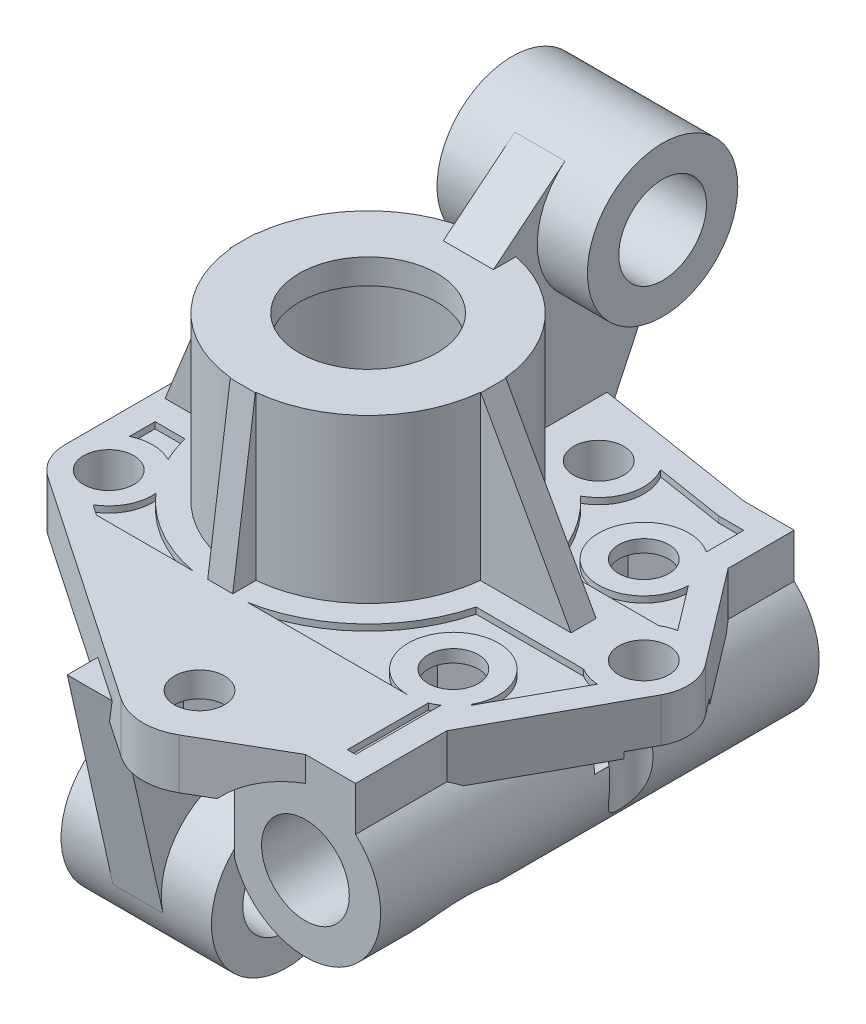
SolidWorks part; units mm, degrees
note: '?' marks a value the reader was unsure of.
ref_plane "Front Plane" through (0, 0, 0) normal (0, 0, 1) x (1, 0, 0)
ref_plane "Top Plane" through (0, 0, 0) normal (0, 1, 0) x (1, 0, 0)
ref_plane "Right Plane" through (0, 0, 0) normal (1, 0, 0) x (0, 0, -1)
ref_plane "StagePlane" through (0, -6, 0) normal (0, 1, 0) x (-1, 0, 0)
sketch "Sketch4" plane through (0, 0, 0) normal (0, 1, 0) x (1, 0, 0)
  circle A0 centre (0, 0) radius 10
  dimension "D3" = 20
extrude "Boss-Extrude5" add sketch "Sketch4" along normal mid plane 30
ref_axis "Axis2" through (0, -15, 0) along (0, 1, 0)?
sketch "Sketch8" plane through (0, 0, 0) normal (1, 0, 0) x (0, 0, -1)
  line L0 (6, 20.2975) -> (6, -9.7025) construction
  line L1 (0, -15) -> (0, 15) construction
  line L2 (55, 0) -> (-55, 0) construction
  line L3 (13.7105, 19.6519) -> (8, 15)
  line L4 (10, 15) -> (-10, 15) construction
  line L5 (10, -15) -> (10, 15) construction
  line L6 (-18.3556, -16.3085) -> (-22, 0)
  line L7 (17.0662, 0) -> (22.9279, 12.443)
  line L8 (17.0662, 0) -> (8, 0)
  line L9 (-6.5, 0) -> (-22, 0)
  line L10 (-10, -15) -> (10, -15) construction
  line L11 (10, -15) -> (17.0662, 0) construction
  line L12 (-6.5, -15) -> (-6.5, 0)
  line L13 (8, 15) -> (8, 0)
  line L14 (-10, 15) -> (-10, -15) construction
  circle A0 centre (17.5, 15) radius 3.5
  circle A1 centre (-12.5, -15) radius 3.5
  arc A2 (-18.3556, -16.3085) -> (-6.5, -15) centre (-12.5, -15) ccw
  arc A3 (22.9279, 12.443) -> (13.7105, 19.6519) centre (17.5, 15) ccw
  dimension "D5" = 7
  dimension "D7" = 12
  dimension "D1" = 6
  dimension "D2" = 30
  dimension "D3" = 30
  dimension "D4" = 11.5
  dimension "D6" = 15
  dimension "D8" = 2
  dimension "D9" = 12
extrude "Boss-Extrude6" add sketch "Sketch8" along normal mid plane 4
sketch "Sketch16" plane through (0, 0, 0) normal (0, 0, 1) x (1, 0, 0)
  line L0 (9, -6) -> (9, 2)
  line L1 (9, 2) -> (19, 2)
  line L2 (19, 2) -> (19, -1.5279)
  line L3 (0, -15) -> (0, 15) construction
  line L6 (15, -6) -> (15, 11.8947) construction
  line L11 (22.825, -6) -> (-22.825, -6) construction
  arc A0 (9, -6) -> (19, -1.5279) centre (15, -6) ccw
  circle A2 centre (15, -6) radius 3.5
  dimension "D2" = 8
  dimension "D4" = 7
  dimension "D5" = 6
  dimension "D1" = 4
  dimension "D3" = 15
extrude "Boss-Extrude10" add sketch "Sketch16" along normal blind 20 and the other way blind 15
ref_axis "Axis3" through (15, -6, 20) along (0, 0, -1)?
sketch "Sketch19" plane through (0, 0, 0) normal (0, 1, 0) x (1, 0, 0)
  line L0 (0, 19.7153) -> (0, -19.681) construction
  line L1 (0, -23.1) -> (0, 23.1) construction
  line L3 (-11, 0) -> (11, 0) construction
  line L4 (19, 15) -> (9, 15) construction
  line L5 (2, 17.0662) -> (15, 15)
  line L6 (15, -20) -> (15, 15) construction
  line L7 (-16, 8.198) -> (-16, -8.198)
  line L8 (24.787, 2.1173) -> (15, 15)
  line L9 (15, -20) -> (8.5912, -23.6961)
  line L10 (2, 13.7105) -> (2, 8) construction
  line L11 (25.0671, -1.686) -> (15, -20)
  line L14 (19, -20) -> (9, -20) construction
  line L15 (-10.5, 0) -> (25.8384, 0) construction
  line L16 (3.8132, -23.5195) -> (-14.4677, -11.0925)
  line L22 (-2, 17.0662) -> (-14.003, 11.3588)
  line L23 (-2, 17.0662) -> (2, 17.0662)
  circle A0 centre (6.343, -19.798) radius 2
  circle A1 centre (-12.5, 8.198) radius 2
  circle A2 centre (-12.5, -8.198) radius 2
  circle A3 centre (6.4, 12) radius 3.6 construction
  circle A4 centre (6.4, 12) radius 2
  arc A5 (3.8132, -23.5195) -> (8.5912, -23.6961) centre (6.343, -19.798) ccw
  arc A6 (-14.003, 11.3588) -> (-16, 8.198) centre (-12.5, 8.198) ccw
  circle A8 centre (22, 0) radius 2
  arc A9 (-16, -8.198) -> (-14.4677, -11.0925) centre (-12.5, -8.198) ccw
  arc A10 (25.0671, -1.686) -> (24.787, 2.1173) centre (22, 0) ccw
  point P28 (14, -20)
  point P40 (-2, 17.0662)
  point P44 (2, 17.0662)
  dimension "D1" = 4
  dimension "D2" = 7
  dimension "D5" = 4
  dimension "D8" = 4.5
  dimension "D9" = 4
  dimension "D10" = 7
  dimension "D14" = 7.2
  dimension "D3" = 4.4
  dimension "D4" = 11.6
  dimension "D6" = 6.343
  dimension "D7" = 10
  dimension "D11" = 12.5
  dimension "D12" = 7
  dimension "D13" = 13.6
extrude "Boss-Extrude Flange" add sketch "Sketch19" along normal mid plane 4
sketch "Sketch10" plane through (0, 0, 0) normal (1, 0, 0) x (0, 0, -1)
  circle A0 centre (17.5, 15) radius 3.5
  circle A1 centre (-12.5, -15) radius 3.5
  arc A2 (-9.798, -12.7754) -> (-9, -15) centre (-12.5, -15) ccw construction
  circle A3 centre (17.5, 15) radius 3.5 construction
extrude "Cut-Extrude3" cut sketch "Sketch10" against normal through all and the other way through all
sketch "Sketch11" plane through (0, 0, 0) normal (1, 0, 0) x (0, 0, -1)
  circle A0 centre (17.5, 15) radius 6
  circle A1 centre (-12.5, -15) radius 6
  arc A3 (-18.3556, -16.3085) -> (-6.5, -15) centre (-12.5, -15) ccw construction
  arc A4 (22.9279, 12.443) -> (13.7105, 19.6519) centre (17.5, 15) ccw construction
  circle A5 centre (17.5, 15) radius 3.5
  circle A6 centre (17.5, 15) radius 3.5 construction
  circle A7 centre (-12.5, -15) radius 3.5
  arc A8 (-9.798, -12.7754) -> (-9, -15) centre (-12.5, -15) ccw construction
extrude "Boss-Extrude7" add sketch "Sketch11" along normal mid plane 12
sketch "Sketch12" plane through (-6, 0, 0) normal (-1, 0, 0) x (0, 0, 1)
  circle A0 centre (12.5, -15) radius 6
  arc A1 (6.5, -15) -> (8, -11.0314) centre (12.5, -15) ccw construction
extrude "Cut-Extrude4" cut sketch "Sketch12" along normal through all
sketch "Sketch14" plane through (6, 0, 0) normal (1, 0, 0) x (0, 0, -1)
  circle A0 centre (-12.5, -15) radius 6
  arc A1 (-8, -11.0314) -> (-6.5, -15) centre (-12.5, -15) ccw construction
extrude "Cut-Extrude5" cut sketch "Sketch14" along normal through all
sketch "Sketch17" plane through (0, 0, 20) normal (0, 0, 1) x (1, 0, 0)
  circle A0 centre (15, -6) radius 6
  arc A3 (9, -6) -> (19, -1.5279) centre (15, -6) ccw construction
  circle A4 centre (15, -6) radius 3.5 construction
extrude "Cut-Extrude6" cut sketch "Sketch17" along normal blind 6
sketch "Sketch18" plane through (0, 0, -15) normal (0, 0, -1) x (-1, 0, 0)
  circle A0 centre (-15, -6) radius 6
  arc A2 (-19, -1.5279) -> (-9, -6) centre (-15, -6) ccw construction
  circle A3 centre (-15, -6) radius 3.5 construction
extrude "Cut-Extrude7" cut sketch "Sketch18" along normal blind 6
ref_axis "Axis6" through (6.343, 2, 19.798) along (0, -1, 0)?
sketch "Sketch25" plane through (0, 0, 0) normal (1, 0, 0) x (0, 0, -1)
  line L0 (0, 15) -> (-10, 15)
  line L1 (-10, 15) -> (-11.798, 2)
  line L2 (-12.7233, 2) -> (-1.686, 2) construction
  line L3 (0, 11) -> (0, -11) construction
  line L6 (-19.798, 2) -> (-19.798, -2) construction
  line L7 (0, 0) -> (17.0662, 0)
  line L8 (17.0662, 0) -> (17.0662, -2)
  line L9 (17.0662, -2) -> (10, -15)
  line L10 (10, -15) -> (0, -15)
  line L11 (0, -15) -> (0, 0)
  line L13 (-11.798, 2) -> (0, 2)
  line L15 (11, 0) -> (-11, 0) construction
  line L16 (0, 15) -> (0, 2)
  dimension "D1" = 8
extrude "Boss-Extrude13" add sketch "Sketch25" along normal mid plane 2
sketch "Sketch22" plane through (0, 0, 0) normal (0, 0, 1) x (1, 0, 0)
  line L0 (0, -15) -> (0, 0)
  line L1 (11, 0) -> (-11, 0) construction
  line L3 (15, 0) -> (15, -2.5)
  line L4 (15, -12) -> (10, -15)
  line L5 (10, -15) -> (0, -15)
  line L6 (15, -9.5) -> (15, -12)
  line L7 (-10, 15) -> (-16, 0)
  line L8 (-16, 0) -> (0, 0)
  line L11 (10, 15) -> (-10, 15)
  line L12 (-1, 15) -> (-10, 15) construction
  line L13 (-16, 2) -> (-16, -2) construction
  line L16 (10, 15) -> (18.3, 0)
  line L17 (18.3, 0) -> (15, 0)
  line L20 (0, -15) -> (0, 15) construction
  line L21 (24, 2) -> (20, 2) construction
  line L22 (22, 2) -> (22, -2) construction
  line L23 (19.4721, -2) -> (25.0671, -2) construction
  arc A0 (9, -6) -> (19, -1.5279) centre (15, -6) ccw construction
  arc A1 (15, -2.5) -> (15, -9.5) centre (15, -6) ccw
  circle A2 centre (15, -6) radius 3.5 construction
  point P23 (22, 2)
  dimension "D1" = 3.7
extrude "Boss-Extrude12" add sketch "Sketch22" along normal mid plane 2
sketch "Sketch7" plane through (0, 0, 0) normal (0, 1, 0) x (1, 0, 0)
  circle A0 centre (0, 0) radius 7.75
  dimension "D1" = 15.5
extrude "Cut-Extrude Bearing" cut sketch "Sketch7" against normal offset from surface 2 and the other way offset from surface (13 mm away) 2 up to face at (3.078, -15, -1.4429) other way up to face at (0, 15, 0.3053)
sketch "Sketch26" plane through (0, 0, 0) normal (0, 1, 0) x (1, 0, 0)
  circle A0 centre (0, 0) radius 5.5
  dimension "D1" = 11
extrude "Cut-Extrude Shaft" cut sketch "Sketch26" against normal through all and the other way through all
ref_axis "Axis4" through (6, 15, -17.5) along (-1, 0, 0)?
ref_axis "Axis5" through (6, -15, 12.5) along (-1, 0, 0)?
sketch "Sketch20" plane through (0, 2, 0) normal (0, 1, 0) x (1, 0, 0)
  line L1 (15, -20) -> (15, 15) construction
  circle A0 centre (15, 7) radius 2
  circle A2 centre (15, -8.198) radius 2
  dimension "D1" = 4
  dimension "D2" = 8
  dimension "D3" = 11.6
extrude "Cut-Extrude8" cut sketch "Sketch20" against normal up to surface (4.5 mm away)
sketch "Sketch21" plane through (0, 0, 0) normal (0, 1, 0) x (1, 0, 0)
  line L1 (15, 3.5359) -> (18, 5.2679)
  line L2 (18, 5.2679) -> (18, 8.7321)
  line L3 (18, 8.7321) -> (15, 10.4641)
  line L4 (15, 10.4641) -> (12, 8.7321)
  line L5 (12, 8.7321) -> (12, 5.2679)
  line L6 (12, 5.2679) -> (15, 3.5359)
  line L13 (15, -11.6621) -> (18, -9.93)
  line L14 (18, -9.93) -> (18, -6.4659)
  line L15 (18, -6.4659) -> (15, -4.7339)
  line L16 (15, -4.7339) -> (12, -6.4659)
  line L17 (12, -6.4659) -> (12, -9.93)
  line L18 (12, -9.93) -> (15, -11.6621)
  circle A0 centre (15, 7) radius 3 construction
  circle A2 centre (15, -8.198) radius 3 construction
  dimension "D1" = 6
extrude "Cut-Extrude10" cut sketch "Sketch21" against normal blind 2 and the other way blind 1
sketch "Sketch30" plane through (0, -2, 0) normal (0, -1, 0) x (1, 0, 0)
  line L0 (10.5279, 22.5792) -> (10.5279, 20) construction
  line L1 (6.343, 23.2621) -> (3.343, 21.53)
  line L2 (3.343, 21.53) -> (3.343, 18.0659)
  line L3 (3.343, 18.0659) -> (6.343, 16.3339)
  line L4 (6.343, 16.3339) -> (9.343, 18.0659)
  line L5 (9.343, 18.0659) -> (9.343, 21.53)
  line L6 (9.343, 21.53) -> (6.343, 23.2621)
  circle A0 centre (6.343, 19.798) radius 3 construction
  dimension "D1" = 6
extrude "Cut-Extrude15" cut sketch "Sketch30" against normal up to surface and the other way up to next
sketch "Sketch33" plane through (0, -2, 0) normal (0, -1, 0) x (1, 0, 0)
  circle A0 centre (22, 0) radius 2
  circle A1 centre (22, 0) radius 2 construction
extrude "Cut-Extrude18" cut sketch "Sketch33" against normal through all and the other way through all
sketch "Sketch32" plane through (0, -2, 0) normal (0, -1, 0) x (1, 0, 0)
  line L0 (22, 3.6) -> (25.6, 3.6)
  line L1 (25.6, 3.6) -> (25.6, -3.6)
  line L2 (25.6, -3.6) -> (22, -3.6)
  arc A0 (22, 3.6) -> (22, -3.6) centre (22, 0) ccw
  dimension "D1" = 7.2
extrude "Cut-Extrude17" cut sketch "Sketch32" against normal blind 0.5 and the other way blind 0.3
sketch "Sketch35" plane through (0, -2, 0) normal (0, -1, 0) x (1, 0, 0)
  line L0 (0, -23.1) -> (0, 23.1) construction
  line L1 (22, -3.4641) -> (25, -1.7321)
  line L2 (25, -1.7321) -> (25, 1.7321)
  line L3 (25, 1.7321) -> (22, 3.4641)
  line L4 (22, 3.4641) -> (19, 1.7321)
  line L5 (19, 1.7321) -> (19, -1.7321)
  line L6 (19, -1.7321) -> (22, -3.4641)
  circle A0 centre (22, 0) radius 3 construction
  circle A1 centre (22, 0) radius 2 construction
  dimension "D1" = 6
extrude "Cut-Extrude19" cut sketch "Sketch35" along normal blind 3
sketch "Sketch36" plane through (0, 2, 0) normal (0, 1, 0) x (1, 0, 0)
  line L0 (-14, 5.0357) -> (-14, 3)
  line L1 (-4, 11.3137) -> (-4, 13.9006)
  line L2 (-4, 13.9006) -> (-10.2883, 10.9106)
  line L3 (-2, 17.0662) -> (-14.003, 11.3588) construction
  line L4 (-2, 17.0662) -> (-2, 9.798) construction
  line L5 (-16, 8.198) -> (-16, -8.198) construction
  line L6 (17, 12.9749) -> (15, 12.9749)
  line L7 (17, 12.9749) -> (17, 9.9933)
  line L8 (18.5997, 6.9555) -> (21.2815, 3.4254)
  line L9 (21.7912, -3.4938) -> (18.2295, -9.9732)
  line L10 (18.2295, -9.9732) -> (18.1548, -9.9321)
  line L11 (16.343, -18) -> (16.343, -11.5381)
  line L12 (15, 12.9749) -> (9.4877, 13.851)
  line L13 (15, 15) -> (2, 17.0662) construction
  line L14 (-2.1928, -11.798) -> (-9.8723, -11.798)
  line L15 (19, 15) -> (19, 9.7347) construction
  line L16 (24.787, 2.1173) -> (19, 9.7347) construction
  line L17 (19, -12.7233) -> (25.0671, -1.686) construction
  line L18 (2.1928, -11.798) -> (15, -11.798)
  line L19 (16.343, -18) -> (17, -18)
  line L20 (17, -18) -> (17, -11.1913)
  line L21 (19, -12.7233) -> (19, -20) construction
  line L22 (19, -20) -> (15, -20) construction
  line L23 (20.1972, -3) -> (11.619, -3)
  line L24 (20.1972, 3) -> (11.619, 3)
  line L25 (9.9499, -1) -> (17.1933, -1) construction
  line L26 (9.9499, 1) -> (17.1933, 1) construction
  line L27 (-14, -3) -> (-11.619, -3)
  line L28 (-11.619, 3) -> (-14, 3)
  line L29 (-9.8723, -11.798) -> (-10.728, -11.2163)
  line L30 (-14, -3) -> (-14, -5.0357)
  line L31 (-14.4677, -11.0925) -> (3.8132, -23.5195) construction
  arc A0 (-4, 11.3137) -> (-9.0106, 7.9252) centre (0, 0) ccw
  arc A1 (-14, 5.0357) -> (-10.8594, 5.1063) centre (-12.5, 8.198) ccw
  arc A2 (8.1186, 8.8367) -> (9.4877, 13.851) centre (6.4, 12) ccw
  arc A3 (17, 9.9933) -> (18.5997, 6.9555) centre (15, 7) ccw
  arc A4 (21.2815, 3.4254) -> (20.1972, 3) centre (22, 0) ccw
  arc A5 (18.1548, -9.9321) -> (15, -11.798) centre (15, -8.198) ccw
  arc A6 (1, -9.9499) -> (9.9499, -1) centre (0, 0) ccw construction
  arc A7 (-10.8594, -5.1063) -> (-14, -5.0357) centre (-12.5, -8.198) ccw
  arc A8 (-14.003, 11.3588) -> (-16, 8.198) centre (-12.5, 8.198) ccw construction
  arc A10 (16.343, -11.5381) -> (17, -11.1913) centre (15, -8.198) ccw
  arc A11 (25.0671, -1.686) -> (24.787, 2.1173) centre (22, 0) ccw construction
  arc A12 (11.619, 3) -> (8.1186, 8.8367) centre (0, 0) ccw
  arc A13 (20.1972, -3) -> (21.7912, -3.4938) centre (22, 0) ccw
  arc A14 (-11.619, -3) -> (-10.8594, -5.1063) centre (0, 0) ccw
  arc A15 (-16, -8.198) -> (-14.4677, -11.0925) centre (-12.5, -8.198) ccw construction
  arc A16 (-9.0106, -7.9252) -> (-2.1928, -11.798) centre (0, 0) ccw
  arc A17 (-10.728, -11.2163) -> (-9.0106, -7.9252) centre (-12.5, -8.198) ccw
  arc A18 (2.1928, -11.798) -> (11.619, -3) centre (0, 0) ccw
  arc A19 (-9.0106, 7.9252) -> (-10.2883, 10.9106) centre (-12.5, 8.198) ccw
  arc A20 (-10.8594, 5.1063) -> (-11.619, 3) centre (0, 0) ccw
  circle A21 centre (6.4, 12) radius 2 construction
  dimension "D1" = 7.2
  dimension "D2" = 2
  dimension "D17" = 3.6
  dimension "D3" = 2
  dimension "D4" = 2
  dimension "D5" = 2
  dimension "D6" = 2
  dimension "D7" = 2
  dimension "D8" = 2
  dimension "D9" = 2
  dimension "D10" = 8
  dimension "D11" = 10
  dimension "D12" = 2
  dimension "D13" = 2
  dimension "D14" = 2
  dimension "D15" = 2
  dimension "D16" = 2
extrude "Cut-Extrude20" cut sketch "Sketch36" against normal blind 0.5
sketch "Sketch37" plane through (0, -2, 0) normal (0, -1, 0) x (1, 0, 0)
  circle A0 centre (6.4, -12) radius 3.6
  dimension "D1" = 7.2
extrude "Cut-Extrude21" cut sketch "Sketch37" along normal through all
split "Split1" [suppressed] bodies to split 127 134 148
